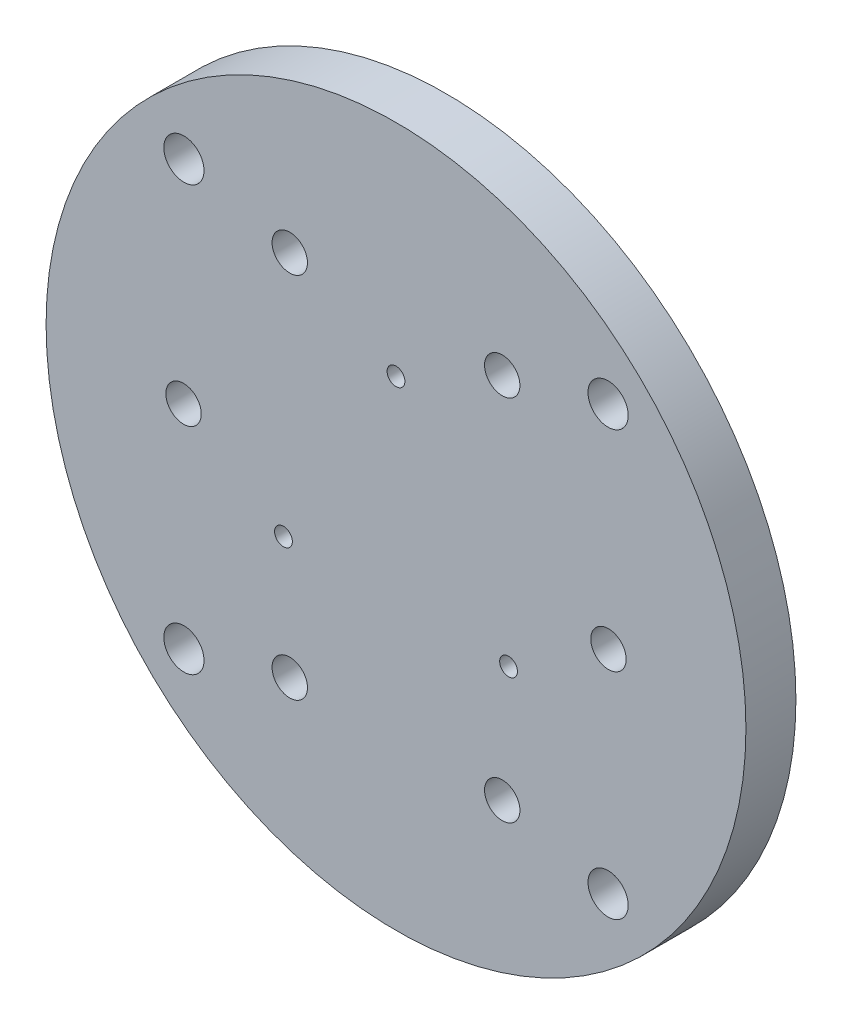
SolidWorks part; units mm, degrees
material "6061-T6 (SS)"
ref_plane "Front Plane" through (0, 0, 0) normal (0, 0, 1) x (1, 0, 0)
ref_plane "Top Plane" through (0, 0, 0) normal (0, 1, 0) x (1, 0, 0)
ref_plane "Right Plane" through (0, 0, 0) normal (1, 0, 0) x (0, 0, -1)
sketch "Sketch1" plane through (0, 0, 0) normal (0, 0, 1) x (1, 0, 0)
  circle A0 centre (0, 0) radius 44.45
  dimension "D1" = 88.9
extrude "Boss-Extrude1" add sketch "Sketch1" along normal blind 6.35
hole_wizard "CSK for #8 Flat Head Machine Screw1" positions "Sketch2" profile "Sketch3" countersink size "#8" standard "ANSI Inch" end condition through all
sketch "Sketch2" plane through (0, 0, 0) normal (0, 0, -1) x (-1, 0, 0)
  line L0 (-13.4937, 23.3719) -> (0, 0) construction
  line L1 (0, 0) -> (0, 26.9875) construction
  circle A0 centre (0, 0) radius 26.9875
  point P5 (-13.4937, 23.3719)
  dimension "D1" = 53.975
  dimension "D2" = 30
sketch "Sketch3" plane through (13.4937, 23.3719, 0) normal (1, 0, 0) x (0, 1, 0)
  line L0 (0, 0) -> (0, 6.35)
  line L1 (0, 6.35) -> (2.2479, 6.35)
  line L2 (2.2479, 6.35) -> (2.2479, 3.0265)
  line L3 (2.2479, 3.0265) -> (4.8788, 0)
  line L5 (4.8788, 0) -> (0, 0)
  line L6 (-2.2479, 3.0265) -> (-4.8788, 0) construction
  line L11 (0, -6.35) -> (0, 107.95) construction
  dimension "Thru Hole Dia." = 4.4958
  dimension "Thru Hole Depth" = 6.35
  dimension "Near C'Sink Dia." = 9.7576
  dimension "Near C'Sink Angle" = 82
pattern_circular "CirPattern1" count 6 over 360 about axis through (0, 0, 6.35) along (0, 0, -1) of "CSK for #8 Flat Head Machine Screw1"
hole_wizard "#10 Clearance Hole1" positions "Sketch4" profile "Sketch5" hole size "#10" standard "ANSI Inch" end condition through all
sketch "Sketch4" plane through (0, 0, 6.35) normal (0, 0, 1) x (1, 0, 0)
  line L0 (0, 38.1) -> (0, 0) construction
  line L1 (0, 0) -> (26.9408, 26.9408) construction
  circle A0 centre (0, 0) radius 38.1
  point P9 (26.9408, 26.9408)
  dimension "D1" = 76.2
  dimension "D2" = 45
sketch "Sketch5" plane through (26.9408, 26.9408, 6.35) normal (1, 0, 0) x (0, -1, 0)
  line L0 (0, 0) -> (0, 6.35)
  line L1 (0, 6.35) -> (2.5527, 6.35)
  line L2 (2.5527, 6.35) -> (2.5527, 0)
  line L5 (2.5527, 0) -> (0, 0)
  line L11 (0, -6.35) -> (0, 107.95) construction
  dimension "Thru Hole Dia." = 5.1054
  dimension "Thru Hole Depth" = 6.35
pattern_circular "CirPattern2" count 4 over 360 about axis through (0, 0, 6.35) along (0, 0, -1) of "#10 Clearance Hole1"
hole_wizard "#4-40 Tapped Hole1" positions "Sketch6" profile "Sketch7" tap size "#4-40" standard "ANSI Inch" end condition through all
sketch "Sketch6" plane through (0, 0, 6.35) normal (0, 0, 1) x (1, 0, 0)
  circle A0 centre (0, 0) radius 16.51
  point P5 (0, 16.51)
  dimension "D1" = 33.02
sketch "Sketch7" plane through (0, 16.51, 6.35) normal (1, 0, 0) x (0, -1, 0)
  line L0 (0, 0) -> (0, 6.35)
  line L1 (0, 6.35) -> (1.1303, 6.35)
  line L2 (1.1303, 6.35) -> (1.1303, 0)
  line L5 (1.1303, 0) -> (0, 0)
  line L11 (0, -6.35) -> (0, 107.95) construction
  dimension "Thru Tap Drill Dia." = 2.2606
  dimension "Thru Tap Drill Depth" = 6.35
cosmetic thread "Hole Thread1" parameters "D2"=2.8448
pattern_circular "CirPattern3" count 3 over 360 about axis through (0, 0, 6.35) along (0, 0, -1) of "#4-40 Tapped Hole1"
